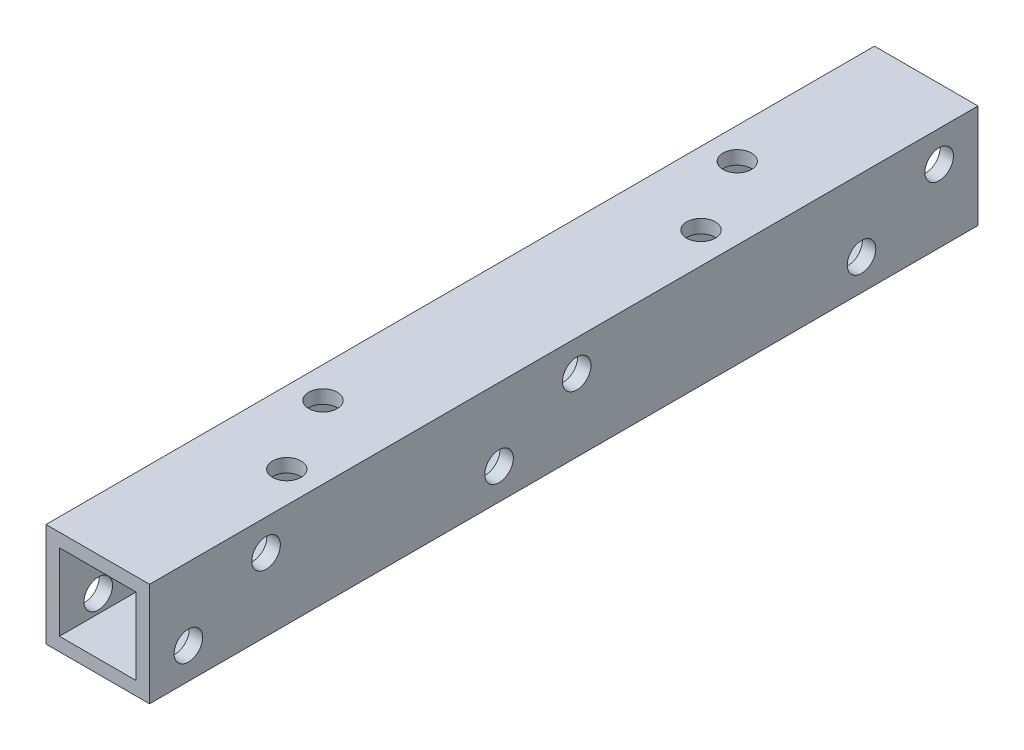
SolidWorks part; units mm, degrees
ref_plane "Front Plane" through (0, 0, 0) normal (1, 0, 0) x (0, 1, 0)
ref_plane "Top Plane" through (0, 0, 0) normal (0, 0, 1) x (0, 1, 0)
ref_plane "Right Plane" through (0, 0, 0) normal (0, 1, 0) x (-1, 0, 0)
sketch "Sketch1" plane through (0, 0, 0) normal (0, 0, 1) x (0, 1, 0)
  line L1 (6.35, -6.35) -> (-6.35, -6.35)
  line L2 (6.35, -6.35) -> (6.35, 6.35)
  line L3 (6.35, 6.35) -> (-6.35, 6.35)
  line L4 (-6.35, -6.35) -> (-6.35, 6.35)
  line L5 (6.35, -6.35) -> (-6.35, 6.35) construction
  line L6 (6.35, 6.35) -> (-6.35, -6.35) construction
  line L7 (4.699, -4.699) -> (-4.699, -4.699)
  line L8 (4.699, -4.699) -> (4.699, 4.699)
  line L9 (4.699, 4.699) -> (-4.699, 4.699)
  line L10 (-4.699, -4.699) -> (-4.699, 4.699)
  line L11 (4.699, -4.699) -> (-4.699, 4.699) construction
  line L12 (4.699, 4.699) -> (-4.699, -4.699) construction
  point P0 (0, 0)
  point P6 (0, 0)
  dimension "D1" = 12.7
  dimension "D2" = 1.651
extrude "Boss-Extrude1" add sketch "Sketch1" along normal blind 101.6
sketch "Sketch2" plane through (0, 6.35, 0) normal (0, 1, 0) x (-1, 0, 0)
  line L0 (-6.35, 50.8) -> (6.35, 50.8) construction
  line L1 (-6.35, 101.6) -> (-6.35, 0) construction
  line L2 (6.35, 101.6) -> (6.35, 0) construction
  line L3 (-6.35, 101.6) -> (6.35, 101.6) construction
  line L12 (2.54, 20.6375) -> (-2.54, 20.6375) construction
  line L15 (2.54, 71.4375) -> (-2.54, 71.4375) construction
  line L16 (2.54, 71.4375) -> (2.54, 80.9625) construction
  line L17 (2.54, 80.9625) -> (-2.54, 80.9625) construction
  line L18 (-2.54, 71.4375) -> (-2.54, 80.9625) construction
  line L19 (2.54, 71.4375) -> (-2.54, 80.9625) construction
  line L20 (2.54, 80.9625) -> (-2.54, 71.4375) construction
  line L21 (2.54, 20.6375) -> (2.54, 30.1625) construction
  line L22 (2.54, 30.1625) -> (-2.54, 30.1625) construction
  line L23 (-2.54, 20.6375) -> (-2.54, 30.1625) construction
  line L24 (2.54, 20.6375) -> (-2.54, 30.1625) construction
  line L25 (2.54, 30.1625) -> (-2.54, 20.6375) construction
  circle A4 centre (-2.54, 80.9625) radius 1.75
  circle A5 centre (2.54, 71.4375) radius 1.75
  circle A6 centre (-2.54, 30.1625) radius 1.75
  circle A7 centre (2.54, 20.6375) radius 1.75
  point P6 (0, 0)
  point P7 (0, 101.6)
  point P8 (0, 25.4)
  point P10 (0, 76.2)
  point P18 (0, 15.2395)
  point P19 (9.572, 22.4671)
  point P20 (0, 0)
  dimension "D2" = 25.4
  dimension "D13" = 3.5
  dimension "D3" = 5.08
  dimension "D4" = 9.525
  dimension "D5" = 25.4
  dimension "D11" = 5.08
  dimension "D12" = 9.525
extrude "Cut-Extrude1" cut sketch "Sketch2" against normal blind 22.2885
sketch "Sketch3" plane through (6.35, 0, 0) normal (1, 0, 0) x (0, 1, 0)
  line L1 (2.54, 4.7625) -> (-2.54, 4.7625) construction
  line L2 (2.54, 4.7625) -> (2.54, 14.2875) construction
  line L7 (2.54, 14.2875) -> (-2.54, 14.2875) construction
  line L11 (-2.54, 4.7625) -> (-2.54, 14.2875) construction
  line L13 (2.54, 4.7625) -> (-2.54, 14.2875) construction
  line L18 (2.54, 14.2875) -> (-2.54, 4.7625) construction
  line L20 (2.54, 87.3125) -> (-2.54, 87.3125) construction
  line L21 (2.54, 87.3125) -> (2.54, 96.8375) construction
  line L22 (2.54, 96.8375) -> (-2.54, 96.8375) construction
  line L23 (-2.54, 87.3125) -> (-2.54, 96.8375) construction
  line L24 (2.54, 87.3125) -> (-2.54, 96.8375) construction
  line L25 (2.54, 96.8375) -> (-2.54, 87.3125) construction
  line L26 (-6.35, 101.6) -> (6.35, 101.6) construction
  line L27 (2.54, 49.2125) -> (-2.54, 49.2125) construction
  line L28 (2.54, 49.2125) -> (2.54, 58.7375) construction
  line L29 (2.54, 58.7375) -> (-2.54, 58.7375) construction
  line L30 (-2.54, 49.2125) -> (-2.54, 58.7375) construction
  line L31 (2.54, 49.2125) -> (-2.54, 58.7375) construction
  line L32 (2.54, 58.7375) -> (-2.54, 49.2125) construction
  line L33 (-6.35, 0) -> (6.35, 0) construction
  circle A8 centre (-2.54, 14.2875) radius 1.75
  circle A9 centre (2.54, 4.7625) radius 1.75
  circle A10 centre (-2.54, 96.8375) radius 1.75
  circle A11 centre (2.54, 87.3125) radius 1.75
  circle A12 centre (-2.54, 58.7375) radius 1.75
  circle A13 centre (2.54, 49.2125) radius 1.75
  point P0 (0, 9.525)
  point P7 (0, 0)
  point P8 (0, 92.075)
  point P15 (0, 53.975)
  point P16 (0, 101.6)
  point P25 (0, 42.8452)
  point P28 (-9.0868, 46.0375)
  point P29 (0, 0)
  dimension "D4" = 3.5
  dimension "D7" = 3.5
  dimension "D11" = 3.5
  dimension "D1" = 5.08
  dimension "D2" = 9.525
  dimension "D3" = 9.525
  dimension "D5" = 5.08
  dimension "D6" = 9.525
  dimension "D8" = 9.525
  dimension "D9" = 5.08
  dimension "D10" = 9.525
  dimension "D12" = 53.975
extrude "Cut-Extrude2" cut sketch "Sketch3" against normal blind 22.098 contours A10 | A11 | A8 | A9 | A12 | A13 region at (6.35, -2.54, 14.2875) region at (6.35, 2.54, 4.7625) region at (6.35, -2.54, 96.8375) region at (6.35, 2.54, 87.3125) region at (6.35, -2.54, 58.7375) region at (6.35, 2.54, 49.2125)
